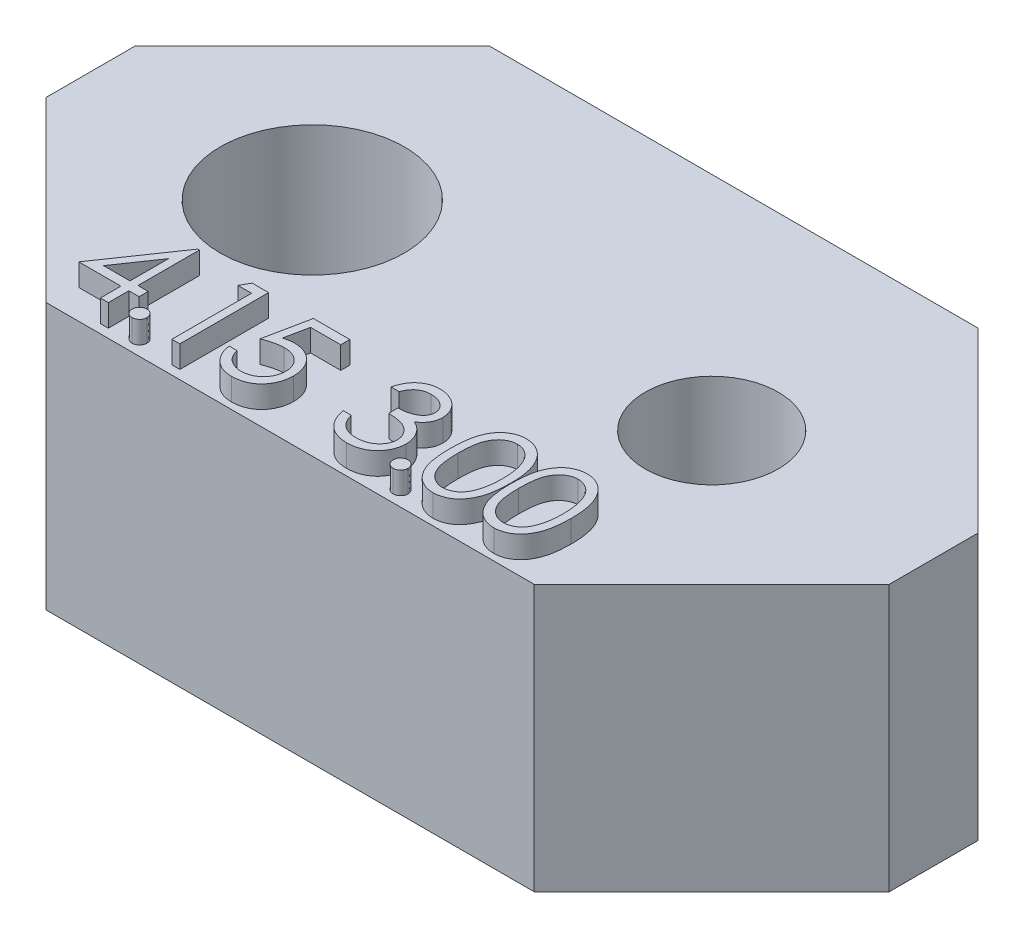
SolidWorks part; units mm, degrees
ref_plane "Спереди" through (0, 0, 0) normal (0, 0, 1) x (1, 0, 0)
ref_plane "Сверху" through (0, 0, 0) normal (0, 1, 0) x (1, 0, 0)
ref_plane "Справа" through (0, 0, 0) normal (1, 0, 0) x (0, 0, -1)
sketch "Эскиз1" plane through (0, 0, 0) normal (0, 1, 0) x (1, 0, 0)
  line L0 (-9.5, 0) -> (9.5, 0) construction
  line L1 (5.5, 5) -> (-5.5, 5)
  line L2 (9.5, 1) -> (9.5, -1)
  line L3 (5.5, -5) -> (-5.5, -5)
  line L4 (-9.5, 1) -> (-9.5, -1)
  line L5 (9.5, 5) -> (-9.5, -5) construction
  line L6 (9.5, -5) -> (-9.5, 5) construction
  line L7 (-5.5, 5) -> (-9.5, 1)
  line L8 (-9.5, -1) -> (-5.5, -5)
  line L9 (9.5, -1) -> (5.5, -5)
  line L10 (5.5, 5) -> (9.5, 1)
  circle A0 centre (-4.5, 0) radius 2.075
  circle A1 centre (4.5, 0) radius 1.5
  point P0 (0, 0)
  dimension "D1" = 4.15
  dimension "D2" = 3
  dimension "D3" = 5
  dimension "D4" = 9
  dimension "D5" = 5
  dimension "D6" = 10
  dimension "D7" = 19
extrude "Бобышка-Вытянуть1" add sketch "Эскиз1" along normal blind 6 contours L10 L1 L7 L4 L8 L3 L9 L2 A1 A0 region at (0.2115, 0, 0)
extrude "Бобышка-Вытянуть2" add sketch "Эскиз1<3>" along normal blind 2 contours A0 | A1 region at (-4.5, 0, 0) region at (4.5, 0, 0)
sketch "Эскиз1<3>" plane through (0, 0, 0) normal (0, 1, 0) x (1, 0, 0) same geometry as "Эскиз1"
sketch "Эскиз3" plane through (0, 6, 0) normal (0, 1, 0) x (1, 0, 0)
  line L0 (-5.5, -5) -> (-5.5, -4.8) construction
  line L1 (-5.5, -4.8) -> (5.5, -4.8) construction
  text T0 "4.15  3.00" font "Century Gothic" height 2
  dimension "D1" = 0.2
  dimension "D2" = 11
extrude "Бобышка-Вытянуть3" add sketch "Эскиз3" along normal blind 0.5
